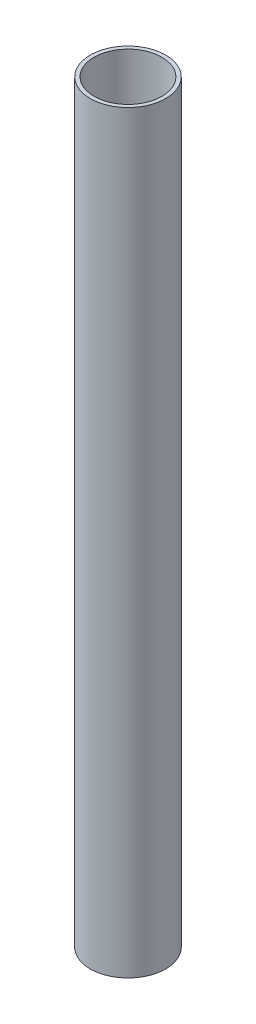
SolidWorks part; units mm, degrees
ref_plane "Front Plane" through (0, 0, 0) normal (0, 0, 1) x (1, 0, 0)
ref_plane "Top Plane" through (0, 0, 0) normal (0, 1, 0) x (1, 0, 0)
ref_plane "Right Plane" through (0, 0, 0) normal (1, 0, 0) x (0, 0, -1)
sketch "Sketch1" plane through (0, 0, 0) normal (0, 1, 0) x (1, 0, 0)
  circle A0 centre (0, 0) radius 20
  circle A1 centre (0, 0) radius 18
  dimension "D1" = 2
  dimension "D2" = 40
extrude "Boss-Extrude1" add sketch "Sketch1" along normal blind 400
ref_plane "Plane1" through (0, 0, 30) normal (0, 0, 1) x (1, 0, 0)
